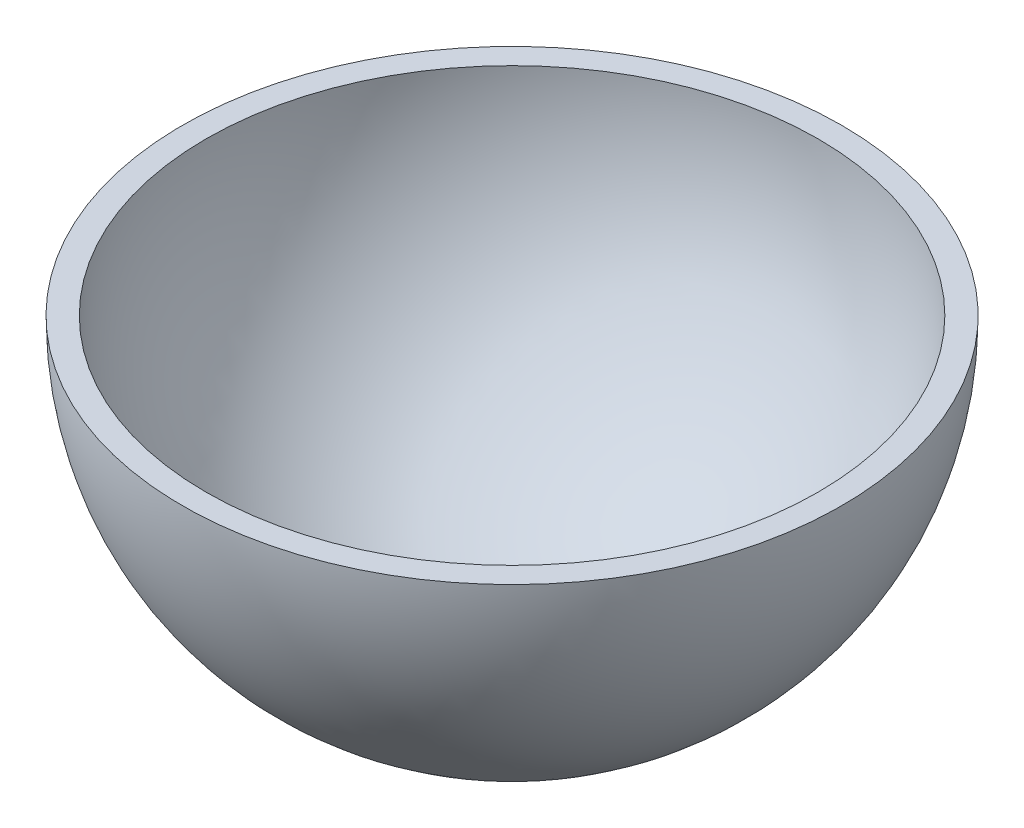
SolidWorks part; units mm, degrees
ref_plane "前视基准面" through (0, 0, 0) normal (0, 0, 1) x (1, 0, 0)
ref_plane "上视基准面" through (0, 0, 0) normal (0, 1, 0) x (1, 0, 0)
ref_plane "右视基准面" through (0, 0, 0) normal (1, 0, 0) x (0, 0, -1)
other "Configuration Table"
sketch "草图1" plane through (0, 0, 0) normal (0, 1, 0) x (1, 0, 0)
  line L0 (35, 0) -> (-35, 0) construction
  line L1 (-35, 0) -> (-32.5, 0)
  line L2 (32.5, 0) -> (35, 0)
  arc A0 (35, 0) -> (-35, 0) centre (0, 0) ccw
  arc A1 (32.5, 0) -> (-32.5, 0) centre (0, 0) ccw
  dimension "D1" = 70
  dimension "D2" = 65
revolve "旋转1" add sketch "草图1" angle 180 about L0
